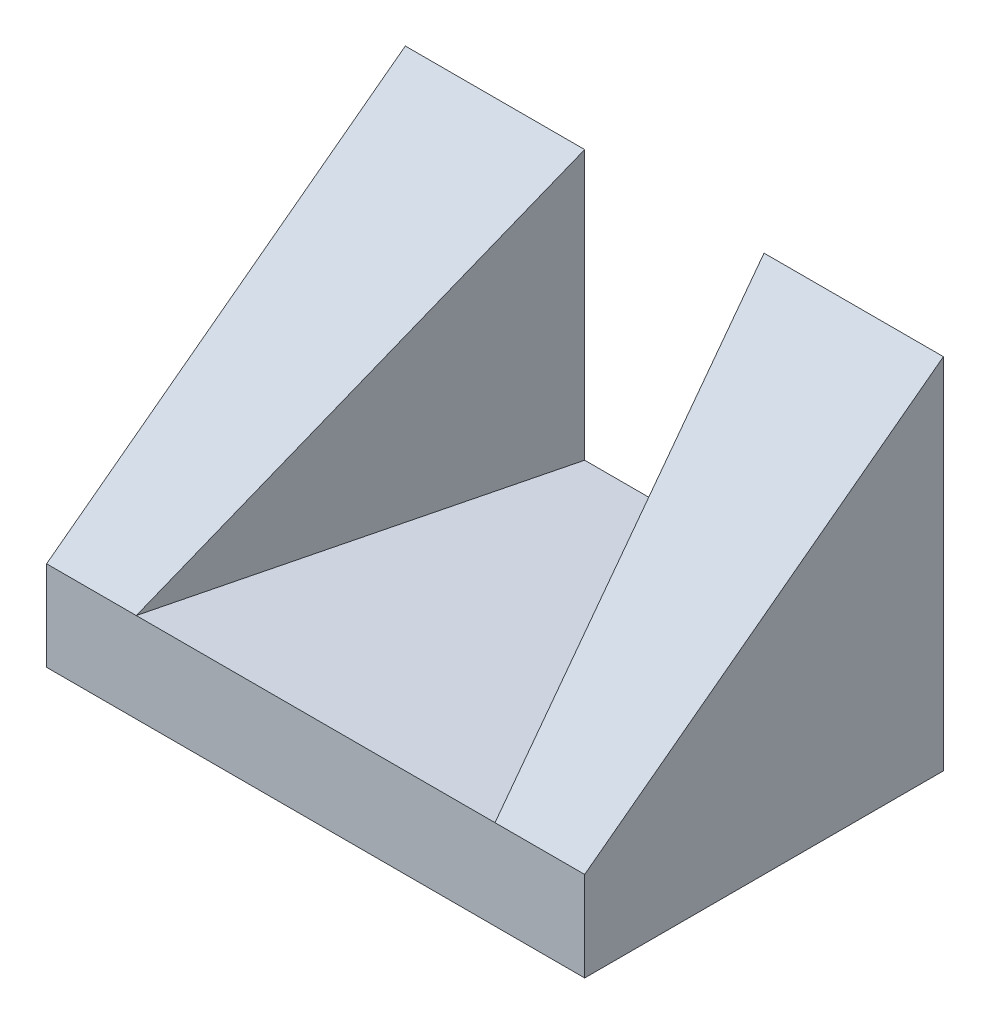
SolidWorks part; units mm, degrees
ref_plane "前基準面" through (0, 0, 0) normal (0, 0, 1) x (1, 0, 0)
ref_plane "上基準面" through (0, 0, 0) normal (0, 1, 0) x (1, 0, 0)
ref_plane "右基準面" through (0, 0, 0) normal (1, 0, 0) x (0, 0, -1)
sketch "草圖1" plane through (0, 0, 0) normal (0, 1, 0) x (1, 0, 0)
  line L0 (-1, 2) -> (-2, -2)
  line L1 (-3, -2) -> (3, -2)
  line L2 (-3, -2) -> (-3, 2)
  line L3 (-3, 2) -> (3, 2)
  line L4 (3, -2) -> (3, 2)
  line L5 (-3, -2) -> (3, 2) construction
  line L6 (-3, 2) -> (3, -2) construction
  line L7 (0, 14.0822) -> (0, -14.3444) construction
  line L8 (1, 2) -> (2, -2)
  point P0 (0, 0)
  dimension "D1" = 6
  dimension "D2" = 4
  dimension "D3" = 1
  dimension "D4" = 2
extrude "填料-伸長1" add sketch "草圖1" along normal blind 1 contours L3 L2 L1 L0 | L8 L3 L0 L1 | L3 L8 L1 L4 region at (0, 0, 0.2222) region at (-2.2222, 0, -0.2222) region at (2.2222, 0, -0.2222)
extrude "填料-伸長2" add sketch "草圖1<3>" along normal blind 4 contours L3 L2 L1 L0 | L3 L8 L1 L4 region at (-2.2222, 0, -0.2222) region at (2.2222, 0, -0.2222)
sketch "草圖1<3>" plane through (0, 0, 0) normal (0, 1, 0) x (1, 0, 0) same geometry as "草圖1"
sketch "草圖2" plane through (3, 0, 0) normal (1, 0, 0) x (0, 0, -1)
  line L0 (2, 4) -> (-2, 1)
  line L1 (-2, 4) -> (-2, 0) construction
  line L5 (-2, 1) -> (-2, 4)
  line L6 (-2, 4) -> (2, 4) construction
  line L7 (-2, 4) -> (2, 4)
  line L8 (-2, 0) -> (-2, 1) construction
  point P5 (-2, 1.0736)
  dimension "D1" = 1
extrude "除料-伸長1" cut sketch "草圖2" against normal blind 9
